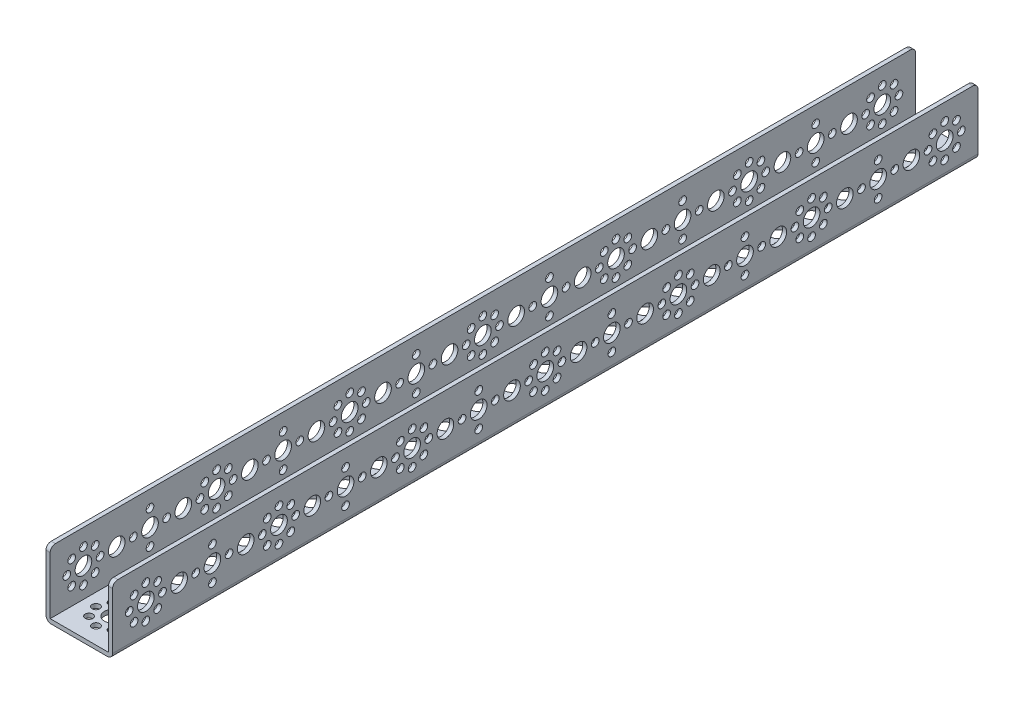
SolidWorks part; units mm, degrees
ref_plane "Front Plane" through (0, 0, 0) normal (0, 0, 1) x (1, 0, 0)
ref_plane "Top Plane" through (0, 0, 0) normal (0, 1, 0) x (1, 0, 0)
ref_plane "Right Plane" through (0, 0, 0) normal (1, 0, 0) x (0, 0, -1)
ref_plane "Plane1" through (-16, 0, 0) normal (-1, 0, 0) x (0, -1, 0)
sketch "Sketch1" plane through (-16, 0, 0) normal (-1, 0, 0) x (0, -1, 0)
  line L0 (-32, -400) -> (0, -400)
  line L1 (0, -400) -> (0, 16)
  line L2 (0, 16) -> (-32, 16)
  line L3 (-32, 16) -> (-32, -400)
extrude "Boss-Extrude1" add sketch "Sketch1" against normal blind 32
sketch "Sketch2" plane through (0, 0, 16) normal (0, 0, 1) x (1, 0, 0)
  line L0 (14, 32) -> (-14, 32)
  line L1 (-14, 32) -> (-14, 2)
  line L2 (-14, 2) -> (14, 2)
  line L3 (14, 2) -> (14, 32)
extrude "Cut-Extrude1" cut sketch "Sketch2" against normal through all
hole_wizard "Ø8.0 (8) Diameter Hole1" positions "Sketch4" profile "Sketch3" hole size "Ø8.0" standard "ANSI Metric"
sketch "Sketch4" plane through (14, 0, 0) normal (-1, 0, 0) x (0, 0, 1)
  point P0 (-32, 16)
sketch "Sketch3" plane through (14, 16, -32) normal (0, 1, 0) x (0, 0, 1)
  line L0 (0, 0) -> (0, 2)
  line L1 (0, 2) -> (4, 2)
  line L2 (4, 2) -> (4, 0)
  line L5 (4, 0) -> (0, 0)
  line L11 (0, -6.35) -> (0, 107.95) construction
  dimension "Thru Hole Dia." = 8
  dimension "Thru Hole Depth" = 2
hole_wizard "Ø8.0 (8) Diameter Hole2" positions "Sketch6" profile "Sketch5" hole size "Ø8.0" standard "ANSI Metric"
sketch "Sketch6" plane through (16, 0, 0) normal (1, 0, 0) x (0, 0, -1)
  point P0 (64, 16)
  point P1 (128, 16)
  point P2 (192, 16)
  point P3 (256, 16)
  point P4 (320, 16)
  point P5 (384, 16)
  point P6 (96, 16)
  point P7 (160, 16)
  point P8 (224, 16)
  point P9 (288, 16)
  point P10 (352, 16)
  point P11 (16, 16)
  point P12 (48, 16)
  point P13 (80, 16)
  point P14 (112, 16)
  point P15 (144, 16)
  point P16 (176, 16)
  point P17 (208, 16)
  point P18 (240, 16)
  point P19 (0, 16)
  point P20 (272, 16)
  point P21 (304, 16)
  point P22 (336, 16)
  point P23 (368, 16)
sketch "Sketch5" plane through (16, 16, -64) normal (0, 1, 0) x (0, 0, -1)
  line L0 (0, 0) -> (0, 2)
  line L1 (0, 2) -> (4, 2)
  line L2 (4, 2) -> (4, 0)
  line L5 (4, 0) -> (0, 0)
  line L11 (0, -6.35) -> (0, 107.95) construction
  dimension "Thru Hole Dia." = 8
  dimension "Thru Hole Depth" = 2
hole_wizard "Ø3.7 (3.7) Diameter Hole1" positions "Sketch8" profile "Sketch7" hole size "Ø3.7" standard "ANSI Metric"
sketch "Sketch8" plane through (16, 0, 0) normal (1, 0, 0) x (0, 0, -1)
  point P0 (0, 24)
  point P1 (0, 8)
  point P2 (8, 16)
  point P3 (-8, 16)
  point P4 (5.6569, 21.6569)
  point P5 (-5.6569, 21.6569)
  point P6 (-5.6569, 10.3431)
  point P7 (5.6569, 10.3431)
  point P8 (64, 24)
  point P9 (64, 8)
  point P10 (72, 16)
  point P11 (56, 16)
  point P12 (69.6569, 21.6569)
  point P13 (58.3431, 21.6569)
  point P14 (58.3431, 10.3431)
  point P15 (69.6569, 10.3431)
  point P16 (128, 24)
  point P17 (128, 8)
  point P18 (136, 16)
  point P19 (120, 16)
  point P20 (133.6569, 21.6569)
  point P21 (122.3431, 21.6569)
  point P22 (122.3431, 10.3431)
  point P23 (133.6569, 10.3431)
  point P24 (192, 24)
  point P25 (192, 8)
  point P26 (200, 16)
  point P27 (184, 16)
  point P28 (197.6569, 21.6569)
  point P29 (186.3431, 21.6569)
  point P30 (186.3431, 10.3431)
  point P31 (197.6569, 10.3431)
  point P32 (256, 24)
  point P33 (256, 8)
  point P34 (264, 16)
  point P35 (248, 16)
  point P36 (261.6569, 21.6569)
  point P37 (250.3431, 21.6569)
  point P38 (250.3431, 10.3431)
  point P39 (261.6569, 10.3431)
  point P40 (320, 24)
  point P41 (320, 8)
  point P42 (328, 16)
  point P43 (312, 16)
  point P44 (325.6569, 21.6569)
  point P45 (314.3431, 21.6569)
  point P46 (314.3431, 10.3431)
  point P47 (325.6569, 10.3431)
  point P48 (384, 24)
  point P49 (384, 8)
  point P50 (392, 16)
  point P51 (376, 16)
  point P52 (389.6569, 21.6569)
  point P53 (378.3431, 21.6569)
  point P54 (378.3431, 10.3431)
  point P55 (389.6569, 10.3431)
  point P56 (32, 24)
  point P57 (40, 16)
  point P58 (32, 8)
  point P59 (24, 16)
  point P60 (96, 24)
  point P61 (104, 16)
  point P62 (96, 8)
  point P63 (88, 16)
  point P64 (160, 24)
  point P65 (168, 16)
  point P66 (160, 8)
  point P67 (152, 16)
  point P68 (224, 24)
  point P69 (232, 16)
  point P70 (224, 8)
  point P71 (216, 16)
  point P72 (288, 24)
  point P73 (296, 16)
  point P74 (288, 8)
  point P75 (280, 16)
  point P76 (352, 24)
  point P77 (360, 16)
  point P78 (352, 8)
  point P79 (344, 16)
sketch "Sketch7" plane through (16, 24, 0) normal (0, 1, 0) x (0, 0, -1)
  line L0 (0, 0) -> (0, 2)
  line L1 (0, 2) -> (1.85, 2)
  line L2 (1.85, 2) -> (1.85, 0)
  line L5 (1.85, 0) -> (0, 0)
  line L11 (0, -6.35) -> (0, 107.95) construction
  dimension "Thru Hole Dia." = 3.7
  dimension "Thru Hole Depth" = 2
hole_wizard "Ø3.7 (3.7) Diameter Hole2" positions "Sketch10" profile "Sketch9" hole size "Ø3.7" standard "ANSI Metric"
sketch "Sketch10" plane through (0, 0, 0) normal (0, -1, 0) x (-1, 0, 0)
  point P0 (8, 0)
  point P1 (5.6569, 5.6569)
  point P2 (0, 8)
  point P3 (-5.6569, 5.6569)
  point P4 (-8, 0)
  point P5 (-5.6569, -5.6569)
  point P6 (0, -8)
  point P7 (5.6569, -5.6569)
  point P8 (8, 64)
  point P9 (5.6569, 69.6569)
  point P10 (0, 72)
  point P11 (-5.6569, 69.6569)
  point P12 (-8, 64)
  point P13 (-5.6569, 58.3431)
  point P14 (0, 56)
  point P15 (5.6569, 58.3431)
  point P16 (8, 128)
  point P17 (5.6569, 133.6569)
  point P18 (0, 136)
  point P19 (-5.6569, 133.6569)
  point P20 (-8, 128)
  point P21 (-5.6569, 122.3431)
  point P22 (0, 120)
  point P23 (5.6569, 122.3431)
  point P24 (8, 192)
  point P25 (5.6569, 197.6569)
  point P26 (0, 200)
  point P27 (-5.6569, 197.6569)
  point P28 (-8, 192)
  point P29 (-5.6569, 186.3431)
  point P30 (0, 184)
  point P31 (5.6569, 186.3431)
  point P32 (8, 256)
  point P33 (5.6569, 261.6569)
  point P34 (0, 264)
  point P35 (-5.6569, 261.6569)
  point P36 (-8, 256)
  point P37 (-5.6569, 250.3431)
  point P38 (0, 248)
  point P39 (5.6569, 250.3431)
  point P40 (8, 320)
  point P41 (5.6569, 325.6569)
  point P42 (0, 328)
  point P43 (-5.6569, 325.6569)
  point P44 (-8, 320)
  point P45 (-5.6569, 314.3431)
  point P46 (0, 312)
  point P47 (5.6569, 314.3431)
  point P48 (8, 384)
  point P49 (5.6569, 389.6569)
  point P50 (0, 392)
  point P51 (-5.6569, 389.6569)
  point P52 (-8, 384)
  point P53 (-5.6569, 378.3431)
  point P54 (0, 376)
  point P55 (5.6569, 378.3431)
  point P56 (8, 32)
  point P57 (0, 40)
  point P58 (-8, 32)
  point P59 (0, 24)
  point P60 (8, 96)
  point P61 (0, 104)
  point P62 (-8, 96)
  point P63 (0, 88)
  point P64 (8, 160)
  point P65 (0, 168)
  point P66 (-8, 160)
  point P67 (0, 152)
  point P68 (8, 224)
  point P69 (0, 232)
  point P70 (-8, 224)
  point P71 (0, 216)
  point P72 (8, 288)
  point P73 (0, 296)
  point P74 (-8, 288)
  point P75 (0, 280)
  point P76 (8, 352)
  point P77 (0, 360)
  point P78 (-8, 352)
  point P79 (0, 344)
sketch "Sketch9" plane through (-8, 0, 0) normal (1, 0, 0) x (0, 0, -1)
  line L0 (0, 0) -> (0, 32)
  line L1 (0, 32) -> (1.85, 32)
  line L2 (1.85, 32) -> (1.85, 0)
  line L5 (1.85, 0) -> (0, 0)
  line L11 (0, -6.35) -> (0, 107.95) construction
  dimension "Thru Hole Dia." = 3.7
  dimension "Thru Hole Depth" = 32
hole_wizard "Ø8.0 (8) Diameter Hole3" positions "Sketch12" profile "Sketch11" hole size "Ø8.0" standard "ANSI Metric"
sketch "Sketch12" plane through (0, 0, 0) normal (0, -1, 0) x (-1, 0, 0)
  point P0 (0, 0)
  point P1 (0, 64)
  point P2 (0, 128)
  point P3 (0, 192)
  point P4 (0, 256)
  point P5 (0, 320)
  point P6 (0, 384)
  point P7 (0, 32)
  point P8 (0, 96)
  point P9 (0, 160)
  point P10 (0, 224)
  point P11 (0, 288)
  point P12 (0, 352)
  point P13 (0, 16)
  point P14 (0, 48)
  point P15 (0, 80)
  point P16 (0, 112)
  point P17 (0, 144)
  point P18 (0, 176)
  point P19 (0, 208)
  point P20 (0, 240)
  point P21 (0, 272)
  point P22 (0, 304)
  point P23 (0, 336)
  point P24 (0, 368)
sketch "Sketch11" plane through (0, 0, 0) normal (1, 0, 0) x (0, 0, -1)
  line L0 (0, 0) -> (0, 32)
  line L1 (0, 32) -> (4, 32)
  line L2 (4, 32) -> (4, 0)
  line L5 (4, 0) -> (0, 0)
  line L11 (0, -6.35) -> (0, 107.95) construction
  dimension "Thru Hole Dia." = 8
  dimension "Thru Hole Depth" = 32
hole_wizard "Ø8.0 (8) Diameter Hole4" positions "Sketch14" profile "Sketch13" hole size "Ø8.0" standard "ANSI Metric"
sketch "Sketch14" plane through (-16, 0, 0) normal (-1, 0, 0) x (0, 0, 1)
  point P0 (-64, 16)
  point P1 (-128, 16)
  point P2 (-192, 16)
  point P3 (-256, 16)
  point P4 (-320, 16)
  point P5 (-384, 16)
  point P6 (-32, 16)
  point P7 (-96, 16)
  point P8 (-160, 16)
  point P9 (-224, 16)
  point P10 (-288, 16)
  point P11 (-352, 16)
  point P12 (-16, 16)
  point P13 (-48, 16)
  point P14 (-80, 16)
  point P15 (-112, 16)
  point P16 (-144, 16)
  point P17 (-176, 16)
  point P18 (-208, 16)
  point P19 (-240, 16)
  point P20 (0, 16)
  point P21 (-272, 16)
  point P22 (-304, 16)
  point P23 (-336, 16)
  point P24 (-368, 16)
sketch "Sketch13" plane through (-16, 16, -64) normal (0, 1, 0) x (0, 0, 1)
  line L0 (0, 0) -> (0, 32)
  line L1 (0, 32) -> (4, 32)
  line L2 (4, 32) -> (4, 0)
  line L5 (4, 0) -> (0, 0)
  line L11 (0, -6.35) -> (0, 107.95) construction
  dimension "Thru Hole Dia." = 8
  dimension "Thru Hole Depth" = 32
hole_wizard "Ø3.7 (3.7) Diameter Hole3" positions "Sketch16" profile "Sketch15" hole size "Ø3.7" standard "ANSI Metric"
sketch "Sketch16" plane through (-16, 0, 0) normal (-1, 0, 0) x (0, 0, 1)
  point P0 (0, 24)
  point P1 (0, 8)
  point P2 (-8, 16)
  point P3 (8, 16)
  point P4 (-5.6569, 21.6569)
  point P5 (5.6569, 21.6569)
  point P6 (5.6569, 10.3431)
  point P7 (-5.6569, 10.3431)
  point P8 (-64, 24)
  point P9 (-64, 8)
  point P10 (-72, 16)
  point P11 (-56, 16)
  point P12 (-69.6569, 21.6569)
  point P13 (-58.3431, 21.6569)
  point P14 (-58.3431, 10.3431)
  point P15 (-69.6569, 10.3431)
  point P16 (-128, 24)
  point P17 (-128, 8)
  point P18 (-136, 16)
  point P19 (-120, 16)
  point P20 (-133.6569, 21.6569)
  point P21 (-122.3431, 21.6569)
  point P22 (-122.3431, 10.3431)
  point P23 (-133.6569, 10.3431)
  point P24 (-192, 24)
  point P25 (-192, 8)
  point P26 (-200, 16)
  point P27 (-184, 16)
  point P28 (-197.6569, 21.6569)
  point P29 (-186.3431, 21.6569)
  point P30 (-186.3431, 10.3431)
  point P31 (-197.6569, 10.3431)
  point P32 (-256, 24)
  point P33 (-256, 8)
  point P34 (-264, 16)
  point P35 (-248, 16)
  point P36 (-261.6569, 21.6569)
  point P37 (-250.3431, 21.6569)
  point P38 (-250.3431, 10.3431)
  point P39 (-261.6569, 10.3431)
  point P40 (-320, 24)
  point P41 (-320, 8)
  point P42 (-328, 16)
  point P43 (-312, 16)
  point P44 (-325.6569, 21.6569)
  point P45 (-314.3431, 21.6569)
  point P46 (-314.3431, 10.3431)
  point P47 (-325.6569, 10.3431)
  point P48 (-384, 24)
  point P49 (-384, 8)
  point P50 (-392, 16)
  point P51 (-376, 16)
  point P52 (-389.6569, 21.6569)
  point P53 (-378.3431, 21.6569)
  point P54 (-378.3431, 10.3431)
  point P55 (-389.6569, 10.3431)
  point P56 (-32, 24)
  point P57 (-40, 16)
  point P58 (-32, 8)
  point P59 (-24, 16)
  point P60 (-96, 24)
  point P61 (-104, 16)
  point P62 (-96, 8)
  point P63 (-88, 16)
  point P64 (-160, 24)
  point P65 (-168, 16)
  point P66 (-160, 8)
  point P67 (-152, 16)
  point P68 (-224, 24)
  point P69 (-232, 16)
  point P70 (-224, 8)
  point P71 (-216, 16)
  point P72 (-288, 24)
  point P73 (-296, 16)
  point P74 (-288, 8)
  point P75 (-280, 16)
  point P76 (-352, 24)
  point P77 (-360, 16)
  point P78 (-352, 8)
  point P79 (-344, 16)
sketch "Sketch15" plane through (-16, 24, 0) normal (0, 1, 0) x (0, 0, 1)
  line L0 (0, 0) -> (0, 32)
  line L1 (0, 32) -> (1.85, 32)
  line L2 (1.85, 32) -> (1.85, 0)
  line L5 (1.85, 0) -> (0, 0)
  line L11 (0, -6.35) -> (0, 107.95) construction
  dimension "Thru Hole Dia." = 3.7
  dimension "Thru Hole Depth" = 32
fillet "Fillet1" radius 2.5 6 edges at (16, 0, -192) (15, 32, -400) (15, 32, 16) (-15, 32, 16) (-15, 32, -400) (-16, 0, -192) tangent propagation no
